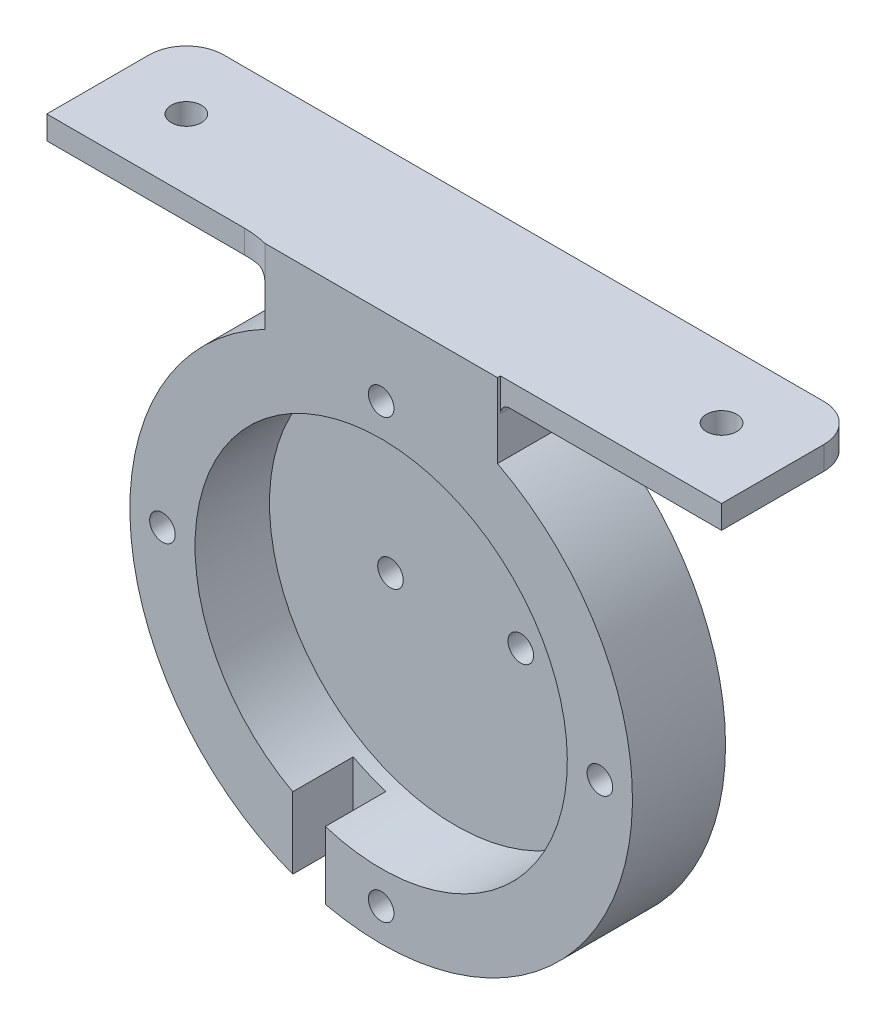
SolidWorks part; units mm, degrees
ref_plane "Front Plane" through (0, 0, 0) normal (0, 0, 1) x (1, 0, 0)
ref_plane "Top Plane" through (0, 0, 0) normal (0, 1, 0) x (1, 0, 0)
ref_plane "Right Plane" through (0, 0, 0) normal (1, 0, 0) x (0, 0, -1)
sketch "Sketch1" plane through (0, 0, 0) normal (0, 0, 1) x (1, 0, 0)
  circle A0 centre (0, 0) radius 27
  circle A1 centre (0, 0) radius 23.5 construction
  circle A2 centre (0, 23.5) radius 1.375
  circle A3 centre (23.5, 0) radius 1.375
  circle A4 centre (0, -23.5) radius 1.375
  circle A5 centre (-23.5, 0) radius 1.375
  circle A6 centre (0, 0) radius 20
  point P15 (0, 0)
  dimension "D1" = 54
  dimension "D2" = 47
  dimension "D3" = 2.75
  dimension "D5" = 40
  dimension "D4" = 4
extrude "Boss-Extrude1" add sketch "Sketch1" along normal blind 10
sketch "Sketch3" plane through (0, 0, 0) normal (0, 0, 1) x (1, 0, 0)
  circle A0 centre (0, 0) radius 20
  circle A1 centre (0, 0) radius 7 construction
  circle A2 centre (-7, 0) radius 1.375
  circle A3 centre (7, 0) radius 1.375
  circle A4 centre (0, 0) radius 11.5 construction
  dimension "D1" = 40
  dimension "D2" = 14
  dimension "D3" = 2.75
  dimension "D4" = 23
extrude "Boss-Extrude2" add sketch "Sketch3" along normal blind 2
sketch "Sketch5" plane through (0, 0, 10) normal (0, 0, 1) x (1, 0, 0)
  line L0 (0, -5.5) -> (0, 5.5) construction
  line L1 (-12.5, 23.9322) -> (-4.2519, 23.9322)
  line L2 (-12.5, 23.9322) -> (-12.5, 31.9322)
  line L3 (-12.5, 31.9322) -> (12.5, 31.9322)
  line L4 (12.5, 23.9322) -> (12.5, 31.9322)
  line L5 (4.2678, 23.9322) -> (0, 26.2545)
  line L6 (0, 26.2545) -> (-4.2519, 23.9322)
  line L7 (4.2678, 23.9322) -> (12.5, 23.9322)
  circle A0 centre (0, 0) radius 27 construction
  dimension "D1" = 12.5
  dimension "D2" = 25
  dimension "D3" = 8
extrude "Boss-Extrude3" add sketch "Sketch5" against normal blind 6
sketch "Sketch4" plane through (0, 0, 0) normal (0, 1, 0) x (1, 0, 0)
  line L1 (-9.5, -3.5) -> (-6, -3.5)
  line L2 (-9.5, -3.5) -> (-9.5, -12.8373)
  line L3 (-9.5, -12.8373) -> (-6, -12.8373)
  line L4 (-6, -3.5) -> (-6, -12.8373)
  line L5 (-29.7, 0) -> (29.7, 0) construction
  dimension "D1" = 3.5
  dimension "D2" = 3.5
  dimension "D4" = 6
extrude "Cut-Extrude1" cut sketch "Sketch4" against normal up to surface (26.3249 mm away) up to face at (0, 11.9661, 7)
sketch "Sketch6" plane through (0, 31.9322, 0) normal (0, 1, 0) x (1, 0, 0)
  line L0 (12.5, -4) -> (12.5, -10) construction
  line L1 (-12.5, -10) -> (12.5, -10)
  line L2 (-12.5, -10) -> (-12.5, 5.32)
  line L3 (-12.5, 5.32) -> (12.5, 5.32)
  line L4 (12.5, -10) -> (12.5, 5.32)
  dimension "D1" = 15.32
extrude "Boss-Extrude4" add sketch "Sketch6" against normal blind 2.5
sketch "Sketch7" plane through (0, 31.9322, 0) normal (0, 1, 0) x (1, 0, 0)
  line L0 (0, -5.5) -> (0, 5.5) construction
  line L1 (-36.25, -67.18) -> (36.25, -67.18) construction
  line L2 (-36.25, -67.18) -> (-36.25, 1.32) construction
  line L3 (-32.25, 5.32) -> (32.25, 5.32) construction
  line L4 (36.25, -67.18) -> (36.25, 1.32) construction
  line L5 (-28.75, -9.68) -> (-36.25, -9.68)
  line L6 (0, 5.32) -> (-36.25, 5.32)
  line L7 (-36.25, -9.68) -> (-36.25, -2.18)
  line L8 (12.5, -4) -> (-12.5, -4) construction
  line L9 (0, 5.32) -> (0, -9.68)
  line L10 (0, -9.68) -> (-28.75, -9.68)
  line L11 (-36.25, 5.32) -> (-36.25, -2.18)
  arc A0 (32.25, 5.32) -> (36.25, 1.32) centre (32.25, 1.32) cw construction
  arc A1 (-36.25, 1.32) -> (-32.25, 5.32) centre (-32.25, 1.32) cw
  circle A3 centre (-28.75, -2.18) radius 1.625
  point P4 (0, 5.32)
  point P11 (36.25, 5.32)
  point P14 (-36.25, 5.32)
  point P21 (-36.25, -9.68)
  dimension "D4" = 4
  dimension "D7" = 3.25
  dimension "D1" = 72.5
  dimension "D2" = 72.5
  dimension "D3" = 9.32
  dimension "D5" = 15
extrude "Boss-Extrude5" add sketch "Sketch7" against normal blind 2.5 contours L10 L9 L6 A1 L11 A3 region at (-17.8481, 31.9322, 2.2226)
fillet "Fillet2" radius 10 1 edges at (-12.5, 30.6822, 9.68)
sketch "Sketch8" plane through (0, 31.9322, 0) normal (0, 1, 0) x (1, 0, 0)
  circle A0 centre (-28.75, -2.18) radius 2.5
  circle A1 centre (-28.75, -2.18) radius 4
  dimension "D1" = 5
  dimension "D2" = 8
extrude "Boss-Extrude6" [suppressed] add sketch "Sketch8" against normal blind 5
mirror "Mirror1" about plane through (0, 0, 0) normal (1, 0, 0) of "Boss-Extrude4", "Boss-Extrude5", "Boss-Extrude6"
fillet "Fillet3" radius 1 3 edges at (0, 29.4322, 4) (12.5, 29.4322, 6.84) (-12.5, 29.4322, 7)
fillet "Fillet4" [suppressed] radius 10
